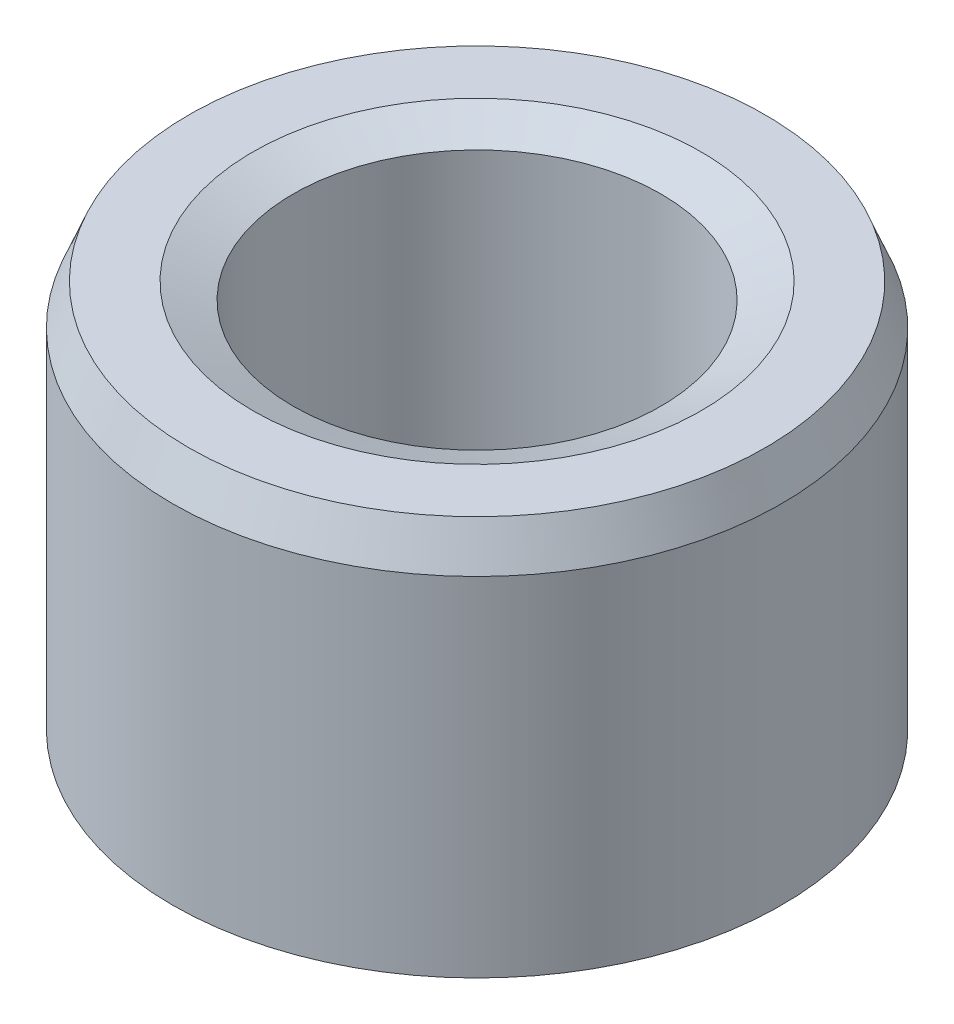
SolidWorks part; units mm, degrees
ref_plane "Front Plane" through (0, 0, 0) normal (0, 0, 1) x (1, 0, 0)
ref_plane "Top Plane" through (0, 0, 0) normal (0, 1, 0) x (1, 0, 0)
ref_plane "Right Plane" through (0, 0, 0) normal (1, 0, 0) x (0, 0, -1)
sketch "Sketch1" plane through (0, 0, 0) normal (0, 1, 0) x (1, 0, 0)
  circle A0 centre (0, 0) radius 20
  dimension "SLEEVE_OD" = 40
extrude "Boss-Extrude1" add sketch "Sketch1" along normal blind 26.5484
sketch "Sketch2" plane through (0, 0, 0) normal (0, 1, 0) x (1, 0, 0)
  circle A0 centre (0, 0) radius 12.0766
  dimension "BORE_D" = 24.1531
extrude "Cut-Extrude1" cut sketch "Sketch2" along normal through all
chamfer "Chamfer1" distance 2.6473 angle 21.961 4 edges at (0, 26.5484, 12.0766) (0, 0, 12.0766) (0, 0, 20) (0, 26.5484, 20) first distance on face at (0, 26.5484, 12.0766) first distance on face at (0, 0, 12.0766) first distance on face at (0, 26.5484, 20)
